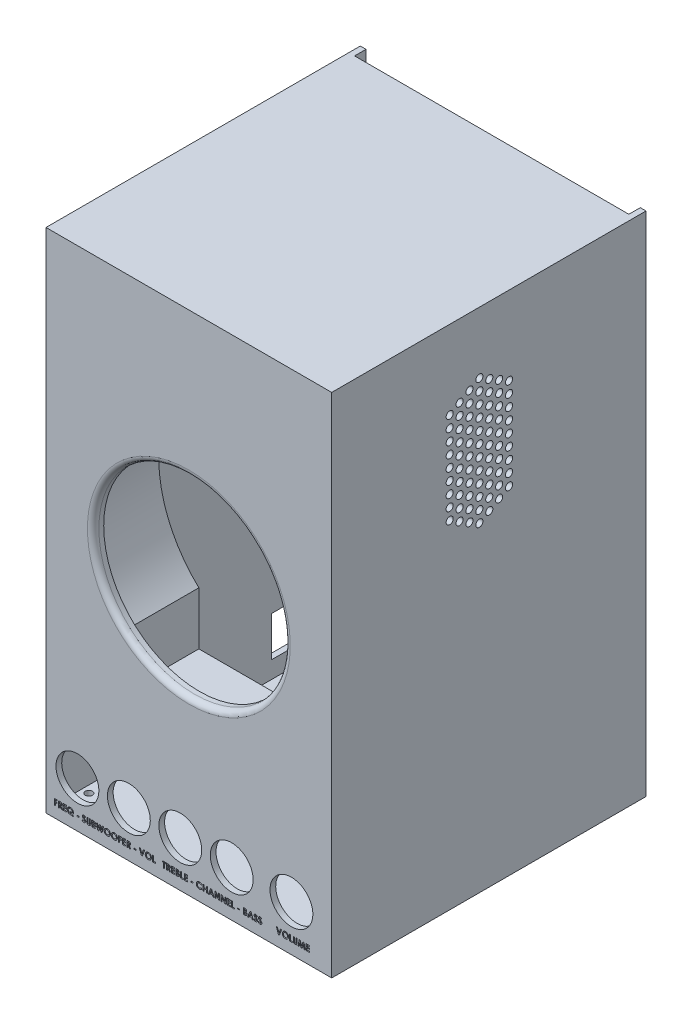
SolidWorks part; units mm, degrees
ref_plane "Front Plane" through (0, 0, 0) normal (0, 0, 1) x (1, 0, 0)
ref_plane "Top Plane" through (0, 0, 0) normal (0, 1, 0) x (1, 0, 0)
ref_plane "Right Plane" through (0, 0, 0) normal (1, 0, 0) x (0, 0, -1)
sketch "Sketch1" plane through (0, 0, 0) normal (1, 0, 0) x (0, 0, -1)
  line L0 (0, 0) -> (110, 0)
  line L1 (110, 0) -> (110, 3)
  line L2 (110, 3) -> (2, 3)
  line L3 (2, 3) -> (2, 34)
  line L7 (0, 177.5) -> (0, 0)
  line L9 (2, 34) -> (27.5, 34)
  line L10 (27.5, 34) -> (27.5, 41)
  line L13 (106, 177.5) -> (0, 177.5)
  line L15 (27.5, 41) -> (34, 41)
  line L16 (34, 41) -> (34, 175.5)
  line L17 (106, 177.5) -> (106, 175.5)
  line L18 (106, 175.5) -> (34, 175.5)
  dimension "D1" = 2
  dimension "D2" = 34
  dimension "D3" = 3
  dimension "D4" = 136.5
  dimension "D5" = 25.5
  dimension "D6" = 31
  dimension "D7" = 38
  dimension "D8" = 110
  dimension "D9" = 2
  dimension "D10" = 106
extrude "Boss-Extrude1" add sketch "Sketch1" along normal blind 96
sketch "Sketch3" plane through (0, 0, -34) normal (0, 0, -1) x (-1, 0, 0)
  line L0 (-48, 41) -> (-48, 42.5) construction
  line L1 (-96, 41) -> (0, 41) construction
  line L5 (-48, 42.5) -> (-48, 93.5) construction
  circle A0 centre (-48, 93.5) radius 44.55
  dimension "D3" = 89.1
  dimension "D1" = 1.5
  dimension "D4" = 51
sketch "Sketch5" plane through (0, 0, -34) normal (0, 0, -1) x (-1, 0, 0)
  line L0 (-48, 41) -> (-48, 175.5) construction
  line L1 (-96, 41) -> (0, 41) construction
  line L2 (-78.5, 42.5) -> (-17.5, 42.5)
  line L3 (-96, 41) -> (0, 41) construction
  line L4 (-78.5, 42.5) -> (-78.5, 61.0277)
  line L5 (-78.5, 61.0277) -> (-17.5, 61.0277)
  line L6 (-17.5, 61.0277) -> (-17.5, 42.5)
  line L7 (-63.35, 175.5) -> (-32.65, 175.5)
  line L8 (-32.65, 175.5) -> (-32.65, 135.322)
  line L9 (-32.65, 135.322) -> (-63.35, 135.322)
  line L10 (-63.35, 135.322) -> (-63.35, 175.5)
  circle A0 centre (-48, 93.5) radius 44.55 construction
  dimension "D1" = 61
  dimension "D2" = 30.7
  dimension "D3" = 133
extrude "Cut-Extrude1" cut sketch "Sketch3" against normal blind 31.3
extrude "Cut-Extrude2" cut sketch "Sketch5" against normal blind 31.3
sketch "Sketch7" plane through (0, 0, -2.7) normal (0, 0, -1) x (-1, 0, 0)
  circle A0 centre (-48, 93.5) radius 35.5
  circle A1 centre (-48, 93.5) radius 44.55 construction
  dimension "D1" = 71
extrude "Boss-Extrude2" add sketch "Sketch7" along normal blind 1
sketch "Sketch6" plane through (0, 0, 0) normal (0, 0, 1) x (1, 0, 0)
  circle A0 centre (48, 93.5) radius 33.5
  arc A1 (32.65, 135.322) -> (17.5, 61.0277) centre (48, 93.5) ccw construction
  dimension "D1" = 67
extrude "Cut-Extrude3" cut sketch "Sketch6" against normal through all
fillet "Fillet1" radius 2 1 edges at (81.5, 93.5, 0)
sketch "Sketch8" plane through (0, 0, -2) normal (0, 0, -1) x (-1, 0, 0)
  line L0 (-96, 16) -> (0, 16) construction
  line L1 (-96, 3) -> (-96, 34) construction
  line L2 (0, 3) -> (0, 34) construction
  line L3 (-96, 3) -> (0, 3) construction
  circle A0 centre (-83.9, 16) radius 7.5
  circle A1 centre (-63, 16) radius 7.5
  circle A2 centre (-45, 16) radius 7.5
  circle A3 centre (-27, 16) radius 7.5
  circle A4 centre (-9, 16) radius 7.5
  dimension "D2" = 15
  dimension "D1" = 13
  dimension "D3" = 63
  dimension "D4" = 45
  dimension "D5" = 27
  dimension "D6" = 9
  dimension "D7" = 20.9
extrude "Cut-Extrude4" cut sketch "Sketch8" against normal through all
sketch "Sketch9" plane through (0, 0, -34) normal (0, 0, -1) x (-1, 0, 0)
  line L0 (-48, 41) -> (-48, 177.5) construction
  line L1 (-96, 41) -> (0, 41) construction
  line L2 (-96, 177.5) -> (0, 177.5) construction
  line L3 (-71.35, 171) -> (-24.65, 171) construction
  line L5 (-71.35, 141) -> (-24.65, 141) construction
  line L6 (-86.5, 55) -> (-9.5, 55) construction
  circle A0 centre (-71.35, 141) radius 1.15
  circle A1 centre (-24.65, 141) radius 1.15
  circle A2 centre (-71.35, 171) radius 1.15
  circle A3 centre (-24.65, 171) radius 1.15
  circle A4 centre (-86.5, 55) radius 1.15
  circle A5 centre (-9.5, 55) radius 1.15
  point P18 (-48, 171)
  point P19 (-48, 141)
  point P20 (-48, 55)
  dimension "D1" = 2.3
  dimension "D2" = 46.7
  dimension "D3" = 77
  dimension "D4" = 14
  dimension "D5" = 100
  dimension "D6" = 30
extrude "Cut-Extrude5" cut sketch "Sketch9" against normal blind 20
sketch "Sketch10" plane through (96, 0, 0) normal (1, 0, 0) x (0, 0, -1)
  line L1 (0, 177.5) -> (110, 177.5)
  line L2 (0, 177.5) -> (0, 0)
  line L3 (0, 0) -> (110, 0)
  line L4 (110, 177.5) -> (110, 0)
extrude "Boss-Extrude3" add sketch "Sketch10" along normal blind 2
sketch "Sketch11" plane through (0, 0, 0) normal (-1, 0, 0) x (0, 0, 1)
  line L1 (0, 177.5) -> (-110, 177.5)
  line L2 (0, 177.5) -> (0, 0)
  line L3 (0, 0) -> (-110, 0)
  line L4 (-110, 177.5) -> (-110, 0)
extrude "Boss-Extrude4" add sketch "Sketch11" along normal blind 2
sketch "Sketch12" plane through (0, 0, 0) normal (0, 0, 1) x (1, 0, 0)
  text T0 "<b>FREQ - SUBWOOFER - VOL   TREBLE - CHANNEL - BASS      VOLUME</b>" font "Century Gothic" height 2.1
extrude "Cut-Extrude6" cut sketch "Sketch12" against normal blind 1
sketch "Sketch13" plane through (0, 3, 0) normal (0, 1, 0) x (1, 0, 0)
  line L0 (96, 110) -> (96, 2) construction
  line L2 (96, 2) -> (0, 2) construction
  line L3 (0, 110) -> (0, 2) construction
  circle A0 centre (2.5, 10.5) radius 1.25
  circle A1 centre (93.5, 10.5) radius 1.25
  circle A2 centre (93.9, 71.5) radius 1.25
  circle A3 centre (2.5, 71.5) radius 1.25
  dimension "D1" = 2.5
  dimension "D2" = 2.5
  dimension "D3" = 8.5
  dimension "D4" = 8.5
  dimension "D5" = 2.5
  dimension "D6" = 2.5
  dimension "D7" = 2.1
  dimension "D8" = 69.5
  dimension "D9" = 69.5
extrude "Cut-Extrude7" cut sketch "Sketch13" against normal through all
sketch "Sketch14" plane through (0, 0, 0) normal (0, -1, 0) x (1, 0, 0)
  circle A0 centre (2.5, -10.5) radius 2.5
  circle A1 centre (93.5, -10.5) radius 2.5
  circle A2 centre (2.5, -71.5) radius 2.5
  circle A3 centre (93.9, -71.5) radius 2.5
  dimension "D1" = 5
extrude "Cut-Extrude8" cut sketch "Sketch14" against normal blind 1
sketch "Sketch16" plane through (0, 0, 0) normal (1, 0, 0) x (0, 0, -1)
  line L0 (110, 177.5) -> (110, 3) construction
  line L1 (110, 9) -> (77, 9)
  line L2 (110, 9) -> (110, 23)
  line L3 (110, 23) -> (77, 23)
  line L4 (77, 9) -> (77, 23)
  line L5 (110, 3) -> (2, 3) construction
  line L6 (2, 3) -> (2, 34) construction
  dimension "D1" = 14
  dimension "D2" = 6
  dimension "D3" = 75
extrude "Cut-Extrude9" cut sketch "Sketch16" against normal through all
sketch "Sketch17" plane through (0, 0, -27.5) normal (0, 0, -1) x (-1, 0, 0)
  line L0 (-96, 34) -> (0, 34) construction
  line L1 (-96, 41) -> (-91.5, 41)
  line L2 (-96, 41) -> (-96, 34)
  line L3 (-96, 34) -> (-91.5, 34)
  line L4 (-91.5, 41) -> (-91.5, 34)
  line L5 (0, 34) -> (0, 41) construction
  line L6 (0, 41) -> (-4.5, 41)
  line L7 (0, 41) -> (0, 34)
  line L8 (0, 34) -> (-4.5, 34)
  line L9 (-4.5, 41) -> (-4.5, 34)
  line L10 (-96, 41) -> (0, 41) construction
  dimension "D1" = 4.5
  dimension "D2" = 4.5
extrude "Cut-Extrude10" cut sketch "Sketch17" against normal blind 25.5
sketch "Sketch18" plane through (96, 0, 0) normal (-1, 0, 0) x (0, 0, 1)
  line L0 (-2, 41) -> (-34, 41) construction
  line L1 (-47, 112) -> (-59, 112) construction
  line L2 (-37, 122) -> (-37, 147) construction
  line L3 (-47, 157) -> (-59, 157) construction
  line L4 (-69, 122) -> (-69, 147) construction
  line L5 (-34, 41) -> (-34, 175.5) construction
  arc A0 (-37, 122) -> (-47, 112) centre (-47, 122) cw construction
  arc A1 (-59, 112) -> (-69, 122) centre (-59, 122) cw construction
  arc A2 (-69, 147) -> (-59, 157) centre (-59, 147) cw construction
  arc A3 (-47, 157) -> (-37, 147) centre (-47, 147) cw construction
  point P12 (-69, 112)
  point P15 (-69, 157)
  point P18 (-37, 157)
  dimension "D5" = 10
  dimension "D1" = 71
  dimension "D2" = 45
  dimension "D3" = 3
  dimension "D4" = 32
sketch "Sketch20" plane through (96, 0, 0) normal (-1, 0, 0) x (0, 0, 1)
  circle A134 centre (-51.6795, 112) radius 1.25
  circle A140 centre (-62.0718, 122) radius 1.25
  circle A141 centre (-58.6077, 120) radius 1.25
  circle A142 centre (-55.1436, 118) radius 1.25
  circle A143 centre (-51.6795, 116) radius 1.25
  circle A144 centre (-48.2154, 114) radius 1.25
  circle A149 centre (-62.0718, 126) radius 1.25
  circle A150 centre (-58.6077, 124) radius 1.25
  circle A151 centre (-55.1436, 122) radius 1.25
  circle A152 centre (-51.6795, 120) radius 1.25
  circle A153 centre (-48.2154, 118) radius 1.25
  circle A154 centre (-44.7513, 116) radius 1.25
  circle A158 centre (-62.0718, 130) radius 1.25
  circle A159 centre (-58.6077, 128) radius 1.25
  circle A160 centre (-55.1436, 126) radius 1.25
  circle A161 centre (-51.6795, 124) radius 1.25
  circle A162 centre (-48.2154, 122) radius 1.25
  circle A163 centre (-44.7513, 120) radius 1.25
  circle A164 centre (-41.2872, 118) radius 1.25
  circle A167 centre (-62.0718, 134) radius 1.25
  circle A168 centre (-58.6077, 132) radius 1.25
  circle A169 centre (-55.1436, 130) radius 1.25
  circle A170 centre (-51.6795, 128) radius 1.25
  circle A171 centre (-48.2154, 126) radius 1.25
  circle A172 centre (-44.7513, 124) radius 1.25
  circle A173 centre (-41.2872, 122) radius 1.25
  circle A176 centre (-62.0718, 138) radius 1.25
  circle A177 centre (-58.6077, 136) radius 1.25
  circle A178 centre (-55.1436, 134) radius 1.25
  circle A179 centre (-51.6795, 132) radius 1.25
  circle A180 centre (-48.2154, 130) radius 1.25
  circle A181 centre (-44.7513, 128) radius 1.25
  circle A182 centre (-41.2872, 126) radius 1.25
  circle A185 centre (-62.0718, 142) radius 1.25
  circle A186 centre (-58.6077, 140) radius 1.25
  circle A187 centre (-55.1436, 138) radius 1.25
  circle A188 centre (-51.6795, 136) radius 1.25
  circle A189 centre (-48.2154, 134) radius 1.25
  circle A190 centre (-44.7513, 132) radius 1.25
  circle A191 centre (-41.2872, 130) radius 1.25
  circle A194 centre (-62.0718, 146) radius 1.25
  circle A195 centre (-58.6077, 144) radius 1.25
  circle A196 centre (-55.1436, 142) radius 1.25
  circle A197 centre (-51.6795, 140) radius 1.25
  circle A198 centre (-48.2154, 138) radius 1.25
  circle A199 centre (-44.7513, 136) radius 1.25
  circle A200 centre (-41.2872, 134) radius 1.25
  circle A203 centre (-62.0718, 150) radius 1.25
  circle A204 centre (-58.6077, 148) radius 1.25
  circle A205 centre (-55.1436, 146) radius 1.25
  circle A206 centre (-51.6795, 144) radius 1.25
  circle A207 centre (-48.2154, 142) radius 1.25
  circle A208 centre (-44.7513, 140) radius 1.25
  circle A209 centre (-41.2872, 138) radius 1.25
  circle A213 centre (-58.6077, 152) radius 1.25
  circle A214 centre (-55.1436, 150) radius 1.25
  circle A215 centre (-51.6795, 148) radius 1.25
  circle A216 centre (-48.2154, 146) radius 1.25
  circle A217 centre (-44.7513, 144) radius 1.25
  circle A218 centre (-41.2872, 142) radius 1.25
  circle A223 centre (-55.1436, 154) radius 1.25
  circle A224 centre (-51.6795, 152) radius 1.25
  circle A225 centre (-48.2154, 150) radius 1.25
  circle A226 centre (-44.7513, 148) radius 1.25
  circle A227 centre (-41.2872, 146) radius 1.25
  circle A233 centre (-51.6795, 156) radius 1.25
  circle A234 centre (-48.2154, 154) radius 1.25
  circle A235 centre (-44.7513, 152) radius 1.25
  circle A236 centre (-41.2872, 150) radius 1.25
  circle A313 centre (-62.0718, 118) radius 1.25
  circle A314 centre (-58.6077, 116) radius 1.25
  circle A315 centre (-55.1436, 114) radius 1.25
  dimension "D7" = 60
extrude "Cut-Extrude11" cut sketch "Sketch20" against normal through all both and the other way through all
